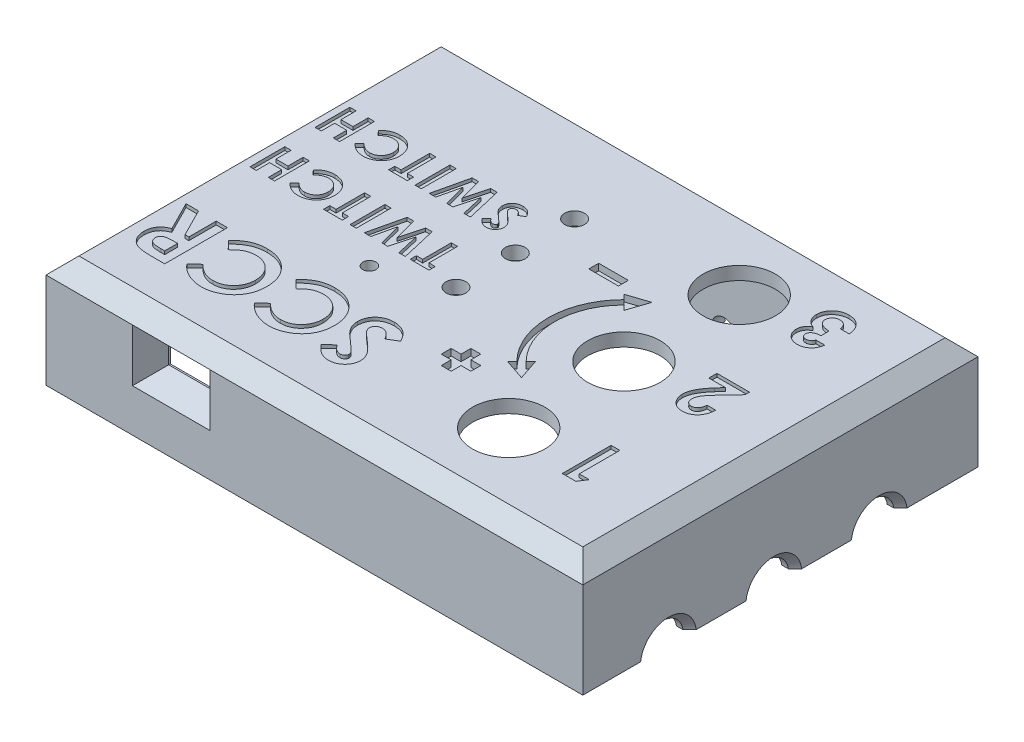
SolidWorks part; units mm, degrees
ref_plane "Front Plane" through (0, 0, 0) normal (0, 0, 1) x (1, 0, 0)
ref_plane "Top Plane" through (0, 0, 0) normal (0, 1, 0) x (1, 0, 0)
ref_plane "Right Plane" through (0, 0, 0) normal (1, 0, 0) x (0, 0, -1)
sketch "Sketch1" plane through (0, 0, 0) normal (0, 1, 0) x (1, 0, 0)
  line L0 (-43.25, 29) -> (38.25, 29)
  line L1 (-41.25, -27) -> (36.25, -27) construction
  line L2 (-41.25, -27) -> (-41.25, 27) construction
  line L3 (-41.25, 27) -> (36.25, 27) construction
  line L4 (36.25, -27) -> (36.25, 27) construction
  line L5 (31.75, -26) -> (-40.25, -26) construction
  line L7 (38.25, -31) -> (38.25, 29)
  line L8 (-43.25, -31) -> (38.25, -31)
  line L9 (-43.25, -31) -> (-43.25, 29)
  point P0 (0, 0)
  point P12 (36.25, 0)
  dimension "D1" = 36.25
  dimension "D2" = 54
  dimension "D4" = 41.25
  dimension "D5" = 31
  dimension "D3" = 29
  dimension "D6" = 38.25
  dimension "D7" = 43.25
extrude "Boss-Extrude1" add sketch "Sketch1" along normal blind 2
sketch "Sketch2" plane through (0, 0, 0) normal (0, -1, 0) x (1, 0, 0)
  line L0 (36.25, 27) -> (36.25, -27) construction
  line L1 (-41.25, -27) -> (36.25, -27) construction
  line L2 (-41.25, 27) -> (-41.25, -27) construction
  line L3 (-41.25, 27) -> (36.25, 27) construction
  line L4 (-43.25, 31) -> (-43.25, -29)
  line L5 (-43.25, -29) -> (38.25, -29)
  line L6 (38.25, -29) -> (38.25, 31)
  line L7 (38.25, 31) -> (-43.25, 31)
  line L8 (-43.25, 31) -> (-43.25, -29)
  line L9 (-43.25, -29) -> (38.25, -29)
  line L10 (38.25, -29) -> (38.25, 31)
  line L11 (38.25, 31) -> (-43.25, 31)
  line L12 (36.25, 27) -> (36.25, -24.25)
  line L13 (-38.5, -27) -> (33.5, -27)
  line L14 (-41.25, 27) -> (-41.25, -24.25)
  line L15 (-41.25, 27) -> (36.25, 27)
  arc A0 (-38.5, -27) -> (-41.25, -24.25) centre (-40.986, -26.736) ccw construction
  arc A1 (36.25, -24.25) -> (33.5, -27) centre (35.986, -26.736) ccw construction
  arc A2 (-38.5, -27) -> (-41.25, -24.25) centre (-40.986, -26.736) ccw
  arc A3 (36.25, -24.25) -> (33.5, -27) centre (35.986, -26.736) ccw
  dimension "D1" = 0
extrude "Boss-Extrude2" add sketch "Sketch2" along normal blind 15
sketch "Sketch3" plane through (0, 0, 31) normal (0, 0, 1) x (1, 0, 0)
  line L0 (-43.25, 2) -> (-43.25, -15) construction
  line L1 (-28.375, -2.25) -> (-20.125, -2.25)
  line L2 (-28.375, -2.25) -> (-28.375, -6.75)
  line L3 (-28.375, -6.75) -> (-20.125, -6.75)
  line L4 (-20.125, -2.25) -> (-20.125, -6.75)
  line L5 (-43.25, 2) -> (38.25, 2) construction
  point P4 (-28.375, -4.5)
  point P6 (-24.25, -2.25)
  dimension "D1" = 4.5
  dimension "D2" = 8.25
  dimension "D3" = 19
  dimension "D4" = 6.5
extrude "Cut-Extrude1" cut sketch "Sketch3" against normal blind 4
chamfer "Chamfer1" distance 1.75 angle 65 4 edges at (-20.125, -4.5, 31) (-24.25, -6.75, 31) (-28.375, -4.5, 31) (-24.25, -2.25, 31) first distance on face at (-24.25, -4.5, 31)
sketch "Sketch4" plane through (0, 0, -29) normal (0, 0, -1) x (-1, 0, 0)
  line L0 (43.25, -15) -> (-38.25, -15) construction
  line L1 (43.25, 2) -> (43.25, -15) construction
  circle A0 centre (-1.7, -14.5) radius 1.875
  circle A1 centre (8, -14.5) radius 1.875
  dimension "D1" = 3.75
  dimension "D2" = 3.75
  dimension "D3" = 9.7
  dimension "D4" = 0.5
  dimension "D5" = 35.25
extrude "Cut-Extrude2" cut sketch "Sketch4" against normal blind 2
sketch "Sketch5" plane through (0, 2, 0) normal (0, 1, 0) x (1, 0, 0)
  line L0 (-38.5, 27) -> (33.5, 27) construction
  circle A0 centre (-8, 14) radius 1.5
  circle A1 centre (-8, 5) radius 1.5
  circle A2 centre (-8, -4) radius 1.5
  dimension "D1" = 3
  dimension "D2" = 13
  dimension "D3" = 9
  dimension "D4" = 9
extrude "Cut-Extrude3" cut sketch "Sketch5" against normal blind 2
sketch "Sketch6" plane through (0, 2, 0) normal (0, 1, 0) x (1, 0, 0)
  line L1 (38.25, 29) -> (-43.25, 29) construction
  circle A0 centre (14.5, 16.5) radius 5.5
  circle A1 centre (14.5, -1) radius 5.5
  circle A2 centre (14.5, -18.5) radius 5.5
  circle A4 centre (-8, -4) radius 1.5 construction
  dimension "D1" = 11
  dimension "D2" = 17.5
  dimension "D3" = 17.5
  dimension "D4" = 22.5
  dimension "D5" = 30
extrude "Cut-Extrude4" cut sketch "Sketch6" against normal blind 2
sketch "Sketch7" plane through (38.25, 0, 0) normal (1, 0, 0) x (0, 0, -1)
  line L0 (29, -15) -> (-31, -15) construction
  line L1 (-31, -31) -> (-31, -15) construction
  circle A0 centre (-18, -15.5) radius 3.25
  circle A1 centre (-2, -15.5) radius 3.25
  circle A2 centre (14, -15.5) radius 3.25
  dimension "D1" = 6.5
  dimension "D2" = 0.5
  dimension "D3" = 16
  dimension "D4" = 16
  dimension "D5" = 13
extrude "Cut-Extrude5" cut sketch "Sketch7" against normal blind 2
fillet "Fillet1" radius 3 2 edges at (36.25, -7.5, 27) (-41.25, -7.5, 27)
sketch "Sketch8" plane through (0, -15, 0) normal (0, -1, 0) x (1, 0, 0)
  circle A0 centre (-40.75, -26.5) radius 1 construction
  circle A1 centre (35.75, -26.5) radius 1 construction
  circle A2 centre (35.75, 28.5) radius 1 construction
  circle A3 centre (-40.75, 28.5) radius 1 construction
  circle A4 centre (-40.75, -26.5) radius 1
  circle A5 centre (35.75, -26.5) radius 1
  circle A6 centre (35.75, 28.5) radius 1
  circle A7 centre (-40.75, 28.5) radius 1
extrude "Cut-Extrude6" cut sketch "Sketch8" against normal blind 8
sketch "Sketch9" plane through (0, 2, 0) normal (0, 1, 0) x (1, 0, 0)
  line L0 (-4.75, -13.5) -> (-39.75, -13.5) construction
  line L1 (-12.25, 1.5) -> (-37.25, 1.5) construction
  line L2 (-43.25, -31) -> (38.25, -31) construction
  line L3 (-43.25, 29) -> (-43.25, -31) construction
  line L4 (-11.75, 11.6202) -> (-37.25, 11.6202) construction
  text T0 "<b>SCCR</b>" font "Century Gothic" height in points 36
  text T1 "<b>TWITCH</b>" font "Century Gothic" height in points 20
  text T2 "SWITCH" font "Century Gothic" height in points 20
  dimension "D1" = 35
  dimension "D2" = 25
  dimension "D3" = 17.5
  dimension "D4" = 3.5
  dimension "D5" = 6
  dimension "D6" = 15
  dimension "D7" = 31.5
extrude "Cut-Extrude7" cut sketch "Sketch9" against normal blind 0.5
sketch "Sketch10" plane through (0, 2, 0) normal (0, 1, 0) x (1, 0, 0)
  line L0 (28.25, -13) -> (23.25, -13) construction
  line L1 (28.25, 4.5) -> (23.25, 4.5) construction
  line L2 (28.25, 22) -> (23.25, 22) construction
  line L4 (38.25, -31) -> (38.25, 29) construction
  circle A0 centre (14.5, -18.5) radius 5.5 construction
  circle A1 centre (14.5, -1) radius 5.5 construction
  circle A2 centre (14.5, 16.5) radius 5.5 construction
  text T0 "<b>1</b>" font "Century Gothic" height in points 28
  text T1 "<b>2</b>" font "Century Gothic" height in points 28
  text T2 "<b>3</b>" font "Century Gothic" height in points 28
  dimension "D1" = 10
  dimension "D2" = 15
extrude "Cut-Extrude8" cut sketch "Sketch10" against normal blind 0.5
sketch "Sketch11" plane through (0, 0, -29) normal (0, 0, -1) x (-1, 0, 0)
  line L0 (-6.85, -10) -> (13.15, -10) construction
  line L1 (-1.7, -14.5) -> (8, -14.5) construction
  line L2 (-3.5071, -15) -> (-38.25, -15) construction
  text T0 "<b>M   P</b>" font "Century Gothic" height in points 16
  point P6 (3.15, -10)
  point P7 (3.15, -14.5)
  dimension "D1" = 20
  dimension "D2" = 5
extrude "Cut-Extrude9" cut sketch "Sketch11" against normal blind 0.5
chamfer "Chamfer2" distance 1 angle 45 3 edges at (38.25, -12.25, -14) (38.25, -12.25, 2) (38.25, -12.25, 18)
fillet "Fillet2" [suppressed] radius 3
sketch "Sketch12" plane through (0, 0, -29) normal (0, 0, -1) x (-1, 0, 0)
  line L0 (-38.25, 2) -> (-38.25, -15) construction
  line L1 (-22.25, -13) -> (-20.75, -13)
  line L2 (-22.25, -13) -> (-22.25, -8)
  line L3 (-22.25, -8) -> (-20.75, -8)
  line L4 (-20.75, -13) -> (-20.75, -8)
  line L5 (-3.5071, -15) -> (-38.25, -15) construction
  circle A0 centre (-31.25, -10.5) radius 2.5
  circle A1 centre (-31.25, -10.5) radius 1.25
  point P11 (-22.25, -10.5)
  dimension "D5" = 5
  dimension "D6" = 2.5
  dimension "D1" = 5
  dimension "D2" = 1.5
  dimension "D3" = 16
  dimension "D4" = 2
  dimension "D7" = 9
sketch "Sketch13" plane through (0, 2, 0) normal (0, 1, 0) x (1, 0, 0)
  circle A0 centre (-17.4, -7.75) radius 1
  circle A1 centre (-8, -4) radius 1.5 construction
  dimension "D3" = 2
  dimension "D1" = 9.4
  dimension "D2" = 3.75
extrude "Cut-Extrude10" cut sketch "Sketch13" against normal up to next
sketch "Sketch14" plane through (0, 2, 0) normal (0, 1, 0) x (1, 0, 0)
  line L0 (5.6612, -9.8388) -> (6.3683, -9.1317)
  line L1 (7.7825, -7.7175) -> (8.8431, -10.8995)
  line L2 (8.8431, -10.8995) -> (5.6612, -9.8388)
  line L3 (4, -1) -> (3, -1) construction
  line L4 (7.0754, -8.4246) -> (6.3683, -9.1317) construction
  line L5 (8.8431, -10.8995) -> (6.7218, -8.7782) construction
  line L6 (7.0754, -8.4246) -> (7.7825, -7.7175)
  line L7 (8.8431, 8.8995) -> (6.7218, 6.7782) construction
  line L8 (7.0754, 6.4246) -> (6.3683, 7.1317) construction
  line L9 (7.0754, 6.4246) -> (7.7825, 5.7175)
  line L10 (8.8431, 8.8995) -> (5.6612, 7.8388)
  line L11 (7.7825, 5.7175) -> (8.8431, 8.8995)
  line L12 (5.6612, 7.8388) -> (6.3683, 7.1317)
  line L13 (1.1612, -13.8995) -> (-0.3388, -13.8995)
  line L14 (2.6612, -15.3995) -> (1.1612, -15.3995)
  line L15 (2.6612, -15.3995) -> (2.6612, -13.8995)
  line L16 (2.6612, -10.8995) -> (1.1612, -10.8995)
  line L17 (1.1612, -15.3995) -> (1.1612, -13.8995)
  line L18 (4.1612, -13.8995) -> (2.6612, -13.8995)
  line L19 (4.1612, -13.8995) -> (4.1612, -12.3995)
  line L20 (4.1612, -12.3995) -> (2.6612, -12.3995)
  line L21 (-0.3388, -13.8995) -> (-0.3388, -12.3995)
  line L22 (4.1612, 8.5) -> (-0.3388, 8.5)
  line L23 (4.1612, 8.5) -> (4.1612, 10)
  line L24 (4.1612, 10) -> (-0.3388, 10)
  line L25 (-0.3388, 8.5) -> (-0.3388, 10)
  line L26 (2.6612, -12.3995) -> (2.6612, -10.8995)
  line L27 (1.1612, -12.3995) -> (-0.3388, -12.3995)
  line L28 (1.1612, -12.3995) -> (1.1612, -10.8995)
  line L29 (2.6612, -13.8995) -> (1.1612, -13.8995) construction
  line L30 (1.9112, -15.3995) -> (1.9112, -10.8995) construction
  line L31 (4.1612, -13.1495) -> (-0.3388, -13.1495) construction
  circle A2 centre (14.5, -1) radius 11.5
  arc A3 (6.3683, 7.1317) -> (6.3683, -9.1317) centre (14.5, -1) ccw
  circle A5 centre (14.5, -1) radius 10.5
  arc A6 (7.0754, 6.4246) -> (7.0754, -8.4246) centre (14.5, -1) ccw
  point P11 (1.9112, -15.3995)
  point P14 (6.7218, -8.7782)
  point P32 (1.9112, -13.8995)
  point P33 (1.9112, -10.8995)
  point P42 (1.9112, -13.1495)
  point P43 (1.9112, -13.1495)
  dimension "D3" = 45
  dimension "D4" = 3
  dimension "D5" = 3
  dimension "D6" = 1
  dimension "D7" = 1.5
  dimension "D8" = 1.5
  dimension "D9" = 1.5
  dimension "D10" = 4.5
  dimension "D11" = 4.5
  dimension "D14" = 0
  dimension "D15" = 9.5
  dimension "D16" = 1.5
  dimension "D1" = 6
  dimension "D2" = 5
extrude "Cut-Extrude11" cut sketch "Sketch14" against normal blind 1
chamfer "Chamfer3" distance 2.5 angle 45 4 edges at (-43.25, 2, 1) (-2.5, 2, -29) (38.25, 2, 1) (-2.5, 2, 31)
